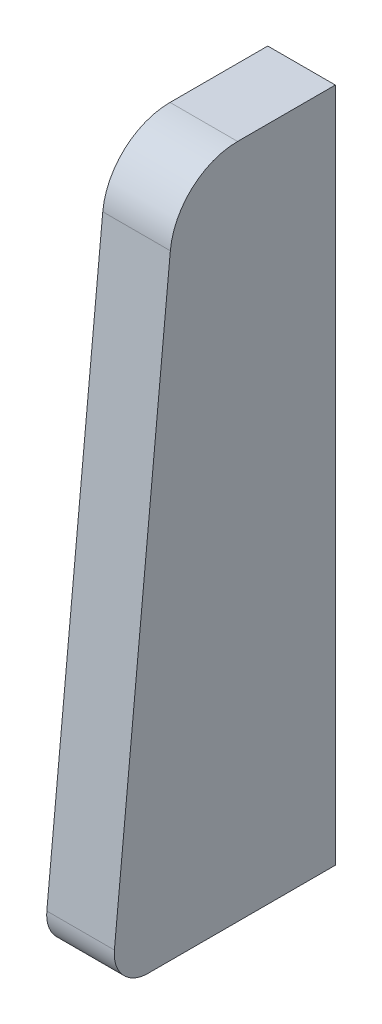
SolidWorks part; units mm, degrees
material "LEXAN (CLEAR)"
ref_plane "Front" through (0, 0, 0) normal (0, 0, 1) x (1, 0, 0)
ref_plane "Top" through (0, 0, 0) normal (0, 1, 0) x (1, 0, 0)
ref_plane "Right" through (0, 0, 0) normal (1, 0, 0) x (0, 0, -1)
ref_axis "Axis1" through (0, 50, 0) along (0, -1, 0)
sketch "Sketch1" plane through (0, 0, 0) normal (1, 0, 0) x (0, 0, -1)
  line L0 (0, 0) -> (0, 127)
  line L1 (0, 127) -> (-29.8968, 127)
  line L2 (-29.8968, 127) -> (-41.5222, 6.9621)
  line L3 (-35.2018, 0) -> (0, 0)
  arc A0 (-41.5222, 6.9621) -> (-35.2018, 0) centre (-35.2018, 6.35) ccw
  point P6 (-42.1965, 0)
  point P9 (0, 0)
  dimension "D1" = 127
  dimension "D4" = 6.35
  dimension "D3" = 90
  dimension "D2" = 42
  dimension "D5" = 5.532
  dimension "D6" = 90
extrude "Boss-Extrude1" add sketch "Sketch1" along normal mid plane 12.7
hole_wizard "#10-24 Tapped Hole1" positions "Sketch3" profile "Sketch2" tap size "#10-24" standard "ANSI Inch"
sketch "Sketch3" plane through (0, 0, 0) normal (0, 0, -1) x (-1, 0, 0)
  line L0 (-6.35, 0) -> (6.35, 0) construction
  point P0 (0, 12.7)
  point P2 (0, 69.85)
  dimension "D1" = 12.7
  dimension "D2" = 69.85
cosmetic thread "Hole Thread2" parameters "D1"=9.525, "D2"=4.826
cosmetic thread "Hole Thread3" parameters "D1"=9.525, "D2"=4.826
sketch "Sketch2" plane through (0, 12.7, 0) normal (1, 0, 0) x (0, 1, 0)
  line L0 (0, 0) -> (0, 16.1014)
  line L1 (0, 16.1014) -> (1.8986, 14.9606)
  line L2 (1.8986, 14.9606) -> (1.8986, 0)
  line L5 (1.8986, 0) -> (0, 0)
  line L10 (0, 16.1014) -> (-1.8987, 14.9606) construction
  line L11 (0, -6.35) -> (0, 107.95) construction
  dimension "Tap Drill Dia." = 3.7973
  dimension "Tap Drill Depth" = 14.9606
  dimension "Drill Angle" = 118
fillet "Fillet1" radius 12.7 1 edges at (0, 127, 29.8968)
